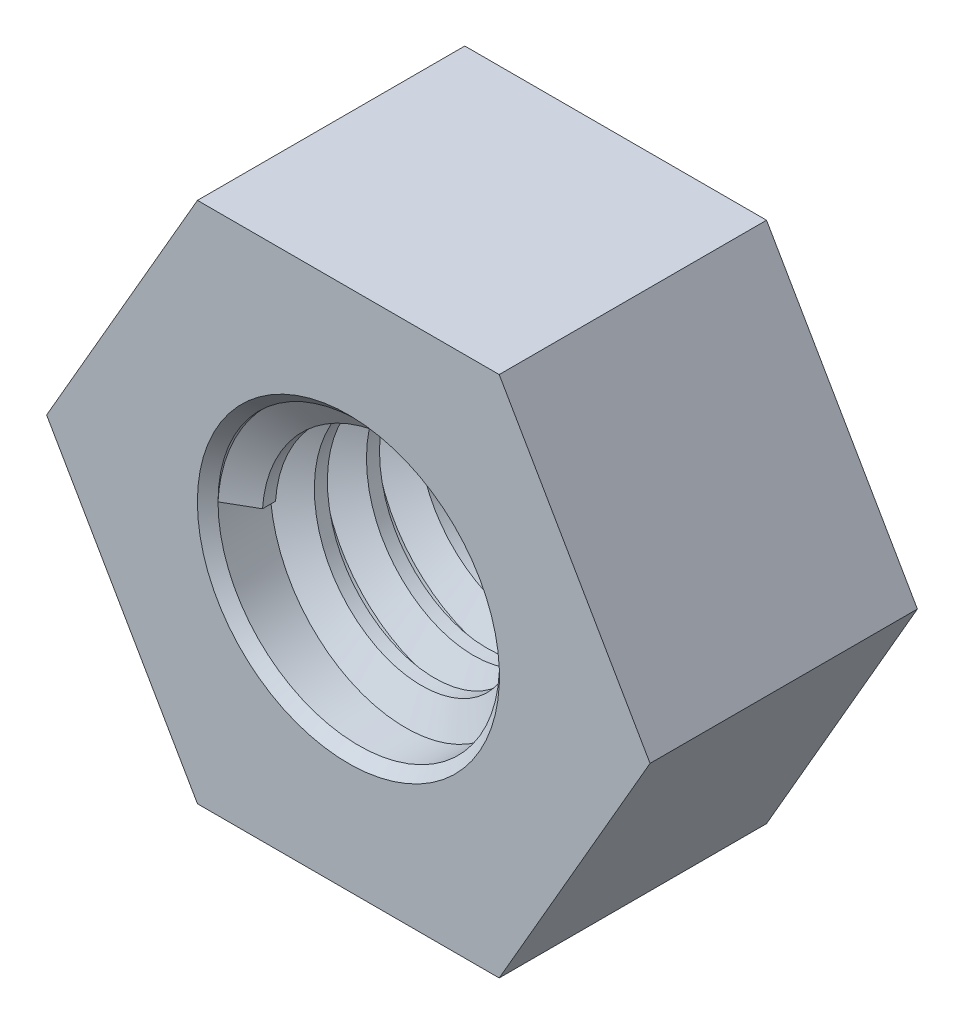
SolidWorks part; units mm, degrees
material "AISI 304"
ref_plane "Front Plane" through (0, 0, 0) normal (0, 0, 1) x (1, 0, 0)
ref_plane "Top Plane" through (0, 0, 0) normal (0, 1, 0) x (1, 0, 0)
ref_plane "Right Plane" through (0, 0, 0) normal (1, 0, 0) x (0, 0, -1)
sketch "Sketch1" plane through (0, 0, 0) normal (0, 0, 1) x (1, 0, 0)
  line L0 (-4.0872, 7.0721) -> (4.083, 7.0721)
  line L1 (4.083, 7.0721) -> (8.1682, -0.0036)
  line L2 (8.1682, -0.0036) -> (4.0831, -7.0792)
  line L3 (4.0831, -7.0792) -> (-4.0872, -7.0792)
  line L4 (-4.0872, -7.0792) -> (-8.1723, -0.0036)
  line L5 (-8.1723, -0.0036) -> (-4.0872, 7.0721)
  circle A0 centre (0, 0) radius 3.81
  circle A1 centre (0, 0) radius 8.1661 construction
  dimension "D1" = 7.62
  dimension "D2" = 16.3322
  dimension "D5" = 4.3561
  dimension "D3" = 8.1702
  dimension "D6" = 4.0831
  dimension "D4" = 6
extrude "Boss-Extrude1" add sketch "Sketch1" along normal mid plane 7.239
chamfer "Chamfer1" distance 0.2794 angle 45 2 edges at (3.81, 0, -3.6195) (3.81, 0, 3.6195)
thread "Thread1" pitch 1.4111 start angle 0, offset 0, length 0, pitch 1.4111, diameter 7.62
ref_plane "Plane2" through (-3.81, 0, 3.3401) normal (0, -1, 0) x (-1, 0, 0)
sketch "Thread Profile2" plane through (-3.81, 0, 3.3401) normal (0, -1, 0) x (-1, 0, 0)
  line L0 (0, 0) -> (0, 1.4111) construction
  line L11 (0, 0) -> (0, 1.2347)
  line L12 (0, 1.2347) -> (-0.7638, 0.7937)
  line L13 (-0.7638, 0.7937) -> (-0.7638, 0.441)
  line L15 (-0.7638, 0.441) -> (0, 0)
  line L17 (-0.7638, 0.6174) -> (0, 0.6174) construction
  point P2 (0, 0)
  dimension "Pitch" = 1.4111
  dimension "Profile_Angle" = 60
  dimension "Profile_Land" = 0.3528
  dimension "Profile_Height" = 0.7638
